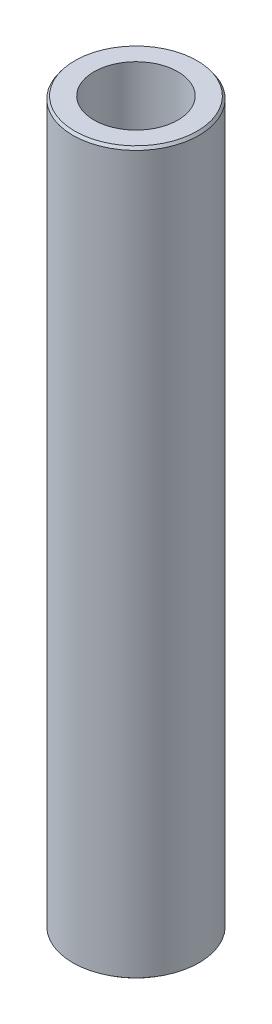
SolidWorks part; units mm, degrees
ref_plane "Front Plane" through (0, 0, 0) normal (0, 0, 1) x (1, 0, 0)
ref_plane "Top Plane" through (0, 0, 0) normal (0, 1, 0) x (1, 0, 0)
ref_plane "Right Plane" through (0, 0, 0) normal (1, 0, 0) x (0, 0, -1)
sketch "Sketch1" plane through (0, 0, 0) normal (0, 1, 0) x (1, 0, 0)
  circle A0 centre (0, 0) radius 52.5
  dimension "SHAFT_OD" = 105
extrude "Boss-Extrude1" add sketch "Sketch1" along normal blind 600
sketch "Sketch2" plane through (0, 0, 0) normal (0, 1, 0) x (1, 0, 0)
  circle A0 centre (0, 0) radius 34.8873
  dimension "BORE_D" = 69.7745
extrude "Cut-Extrude1" cut sketch "Sketch2" along normal through all
chamfer "Chamfer1" distance 2.1802 angle 36.951 2 edges at (0, 600, 52.5) (0, 0, 52.5) first distance on face at (0, 600, 52.5) first distance on face at (0, 0, 34.8873)
